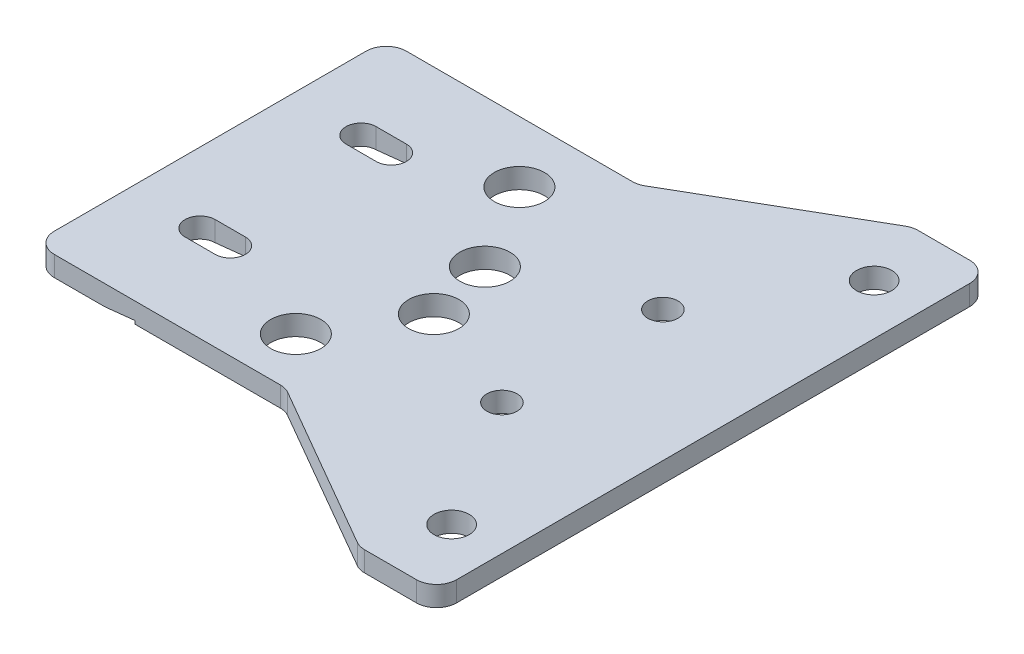
SolidWorks part; units mm, degrees
ref_plane "前视基准面" through (0, 0, 0) normal (0, 0, 1) x (1, 0, 0)
ref_plane "上视基准面" through (0, 0, 0) normal (0, 1, 0) x (1, 0, 0)
ref_plane "右视基准面" through (0, 0, 0) normal (1, 0, 0) x (0, 0, -1)
sketch "草图1" plane through (0, 0, 0) normal (0, 1, 0) x (1, 0, 0)
  line L1 (-25, 27.5) -> (25, 27.5)
  line L2 (-25, 27.5) -> (-25, -27.5)
  line L3 (-25, -27.5) -> (25, -27.5)
  line L4 (25, 27.5) -> (25, -27.5)
  line L5 (-25, 27.5) -> (25, -27.5) construction
  line L6 (-25, -27.5) -> (25, 27.5) construction
  point P0 (0, 0)
  dimension "D1" = 50
  dimension "D2" = 55
extrude "凸台-拉伸1" add sketch "草图1" along normal blind 2
sketch "草图2" plane through (0, 2, 0) normal (0, 1, 0) x (1, 0, 0)
  line L1 (-18, 8) -> (12, 8) construction
  line L2 (-18, 8) -> (-18, -8) construction
  line L3 (-18, -8) -> (12, -8) construction
  line L4 (12, 8) -> (12, -8) construction
  line L5 (-18, 8) -> (12, -8) construction
  line L6 (-18, -8) -> (12, 8) construction
  circle A0 centre (-18, 8) radius 1.5
  circle A1 centre (-18, -8) radius 1.5
  circle A2 centre (12, -8) radius 1.5
  circle A3 centre (12, 8) radius 1.5
  point P0 (-3, 0)
  dimension "D4" = 3
  dimension "D1" = 3
  dimension "D2" = 16
  dimension "D3" = 30
extrude "切除-拉伸1" cut sketch "草图2" against normal through all
sketch "草图3" plane through (0, 0, 0) normal (0, -1, 0) x (1, 0, 0)
  line L4 (-18, 9.5) -> (-15, 9.5)
  line L6 (-15, 6.5) -> (-18, 6.5)
  line L7 (-18, 6.5) -> (-18, 9.5)
  circle A1 centre (-18, 8) radius 1.5 construction
  arc A2 (-15, 6.5) -> (-15, 9.5) centre (-15, 8) ccw
  dimension "D1" = 1.5
  dimension "D2" = 3
extrude "切除-拉伸2" cut sketch "草图3" against normal blind 10
ref_plane "基准面1" through (0, 0, 8) normal (0, 0, 1) x (1, 0, 0)
sketch "草图4" plane through (0, 0, 8) normal (0, 0, 1) x (1, 0, 0)
  line L0 (-18, 0) -> (-15, 0.3153)
  line L1 (-15, 0.3153) -> (-15, 0)
  line L2 (-15, 0) -> (-18, 0)
  dimension "D1" = 6
extrude "切除-拉伸3" cut sketch "草图4" against normal through all both and the other way through all
mirror "镜向1" about plane through (0, 0, 0) normal (0, 0, 1) of "切除-拉伸2"
sketch "草图5" plane through (0, 2, 0) normal (0, 1, 0) x (1, 0, 0)
  line L0 (20, 21) -> (20, -21) construction
  line L1 (25, -27.5) -> (25, 27.5) construction
  circle A0 centre (20, 21) radius 1.75
  circle A1 centre (20, -21) radius 1.75
  point P2 (20, 0)
  dimension "D1" = 3.5
  dimension "D2" = 42
  dimension "D3" = 5
extrude "切除-拉伸4" cut sketch "草图5" against normal blind 10
sketch "草图6" plane through (0, 2, 0) normal (0, 1, 0) x (1, 0, 0)
  line L0 (-25, 17.5) -> (0, 17.5)
  line L1 (-25, 27.5) -> (-25, -27.5) construction
  line L2 (0, 17.5) -> (17.3205, 27.5)
  line L3 (25, 27.5) -> (-25, 27.5) construction
  line L4 (17.3205, 27.5) -> (-25, 27.5)
  line L5 (-25, 27.5) -> (-25, 17.5)
  line L6 (0, 0) -> (-25, 0) construction
  line L7 (17.3205, -27.5) -> (-25, -27.5)
  line L8 (-25, -27.5) -> (-25, -17.5)
  line L9 (0, -17.5) -> (17.3205, -27.5)
  line L10 (-25, -17.5) -> (0, -17.5)
  dimension "D1" = 150
  dimension "D2" = 10
  dimension "D3" = 25
extrude "切除-拉伸5" cut sketch "草图6" against normal blind 10
sketch "草图7" plane through (0, 0, 0) normal (0, -1, 0) x (1, 0, 0)
  line L8 (-4.145, 12.344) -> (1, 3.769) construction
  line L9 (-0.5406, -2.8447) -> (-5.6856, -11.4196) construction
  line L10 (-13.971, 2.9498) -> (6.5877, 15.285) construction
  line L11 (-13.971, -2.9498) -> (6.5877, -15.285) construction
  line L12 (-8.2544, -1.715) -> (14.971, -15.6502) construction
  circle A0 centre (-5.6856, -11.4196) radius 2.5
  circle A1 centre (-0.5406, -2.8447) radius 2.5
  circle A2 centre (-4.145, 12.344) radius 2.5
  circle A3 centre (1, 3.769) radius 2.5
  dimension "D1" = 5
  dimension "D2" = 10
  dimension "D3" = 3
  dimension "D4" = 3
  dimension "D5" = 1
  dimension "D6" = 1
extrude "切除-拉伸6" cut sketch "草图7" against normal blind 10 contours A3 | A2 | A1 | A0 region at (-5.6856, 0, -11.4196) region at (-0.5406, 0, -2.8447) region at (-4.145, 0, 12.344) region at (1, 0, 3.769)
fillet "圆角1" radius 2 8 edges at (17.3205, 1, -27.5) (25, 1, -27.5) (17.3205, 1, 27.5) (-25, 1, -17.5) (0, 1, -17.5) (-25, 1, 17.5) (25, 1, 27.5) (0, 1, 17.5)
